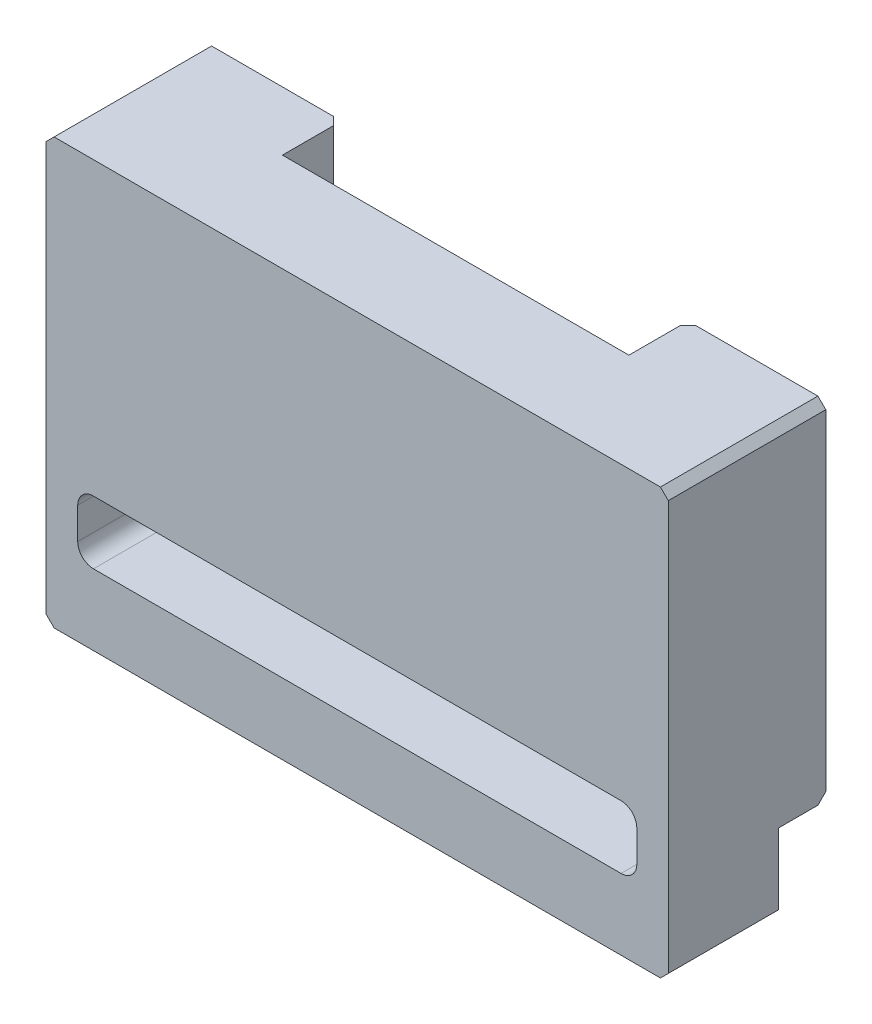
SolidWorks part; units mm, degrees
ref_plane "Front Plane" through (0, 0, 0) normal (0, 0, 1) x (1, 0, 0)
ref_plane "Top Plane" through (0, 0, 0) normal (0, 1, 0) x (1, 0, 0)
ref_plane "Right Plane" through (0, 0, 0) normal (1, 0, 0) x (0, 0, -1)
sketch "Sketch1" plane through (0, 0, 0) normal (0, 0, 1) x (1, 0, 0)
  line L0 (0, 0) -> (-42, 0) construction
  line L1 (-60.5, 5) -> (18.5, 5)
  line L2 (-60.5, 5) -> (-60.5, -49)
  line L3 (-60.5, -49) -> (18.5, -49)
  line L4 (18.5, 5) -> (18.5, -49)
  line L5 (-55.5, -39) -> (-55.5, -33) construction
  line L6 (13.5, -33) -> (13.5, -39) construction
  line L7 (6.5, -39) -> (-48.5, -39) construction
  dimension "D1" = 5
  dimension "D2" = 5
  dimension "D3" = 5
  dimension "D4" = 10
extrude "Boss-Extrude1" add sketch "Sketch1" along normal blind 5 and the other way blind 15
sketch "Sketch3" plane through (0, 0, -15) normal (0, 0, -1) x (-1, 0, 0)
  line L0 (60.5, 5) -> (60.5, -49) construction
  line L1 (-18.5, -49) -> (60.5, -49)
  line L2 (-18.5, -49) -> (-18.5, -39)
  line L3 (-18.5, -39) -> (60.5, -39)
  line L4 (60.5, -49) -> (60.5, -39)
extrude "Cut-Extrude1" cut sketch "Sketch3" against normal blind 1
sketch "Sketch4" plane through (0, 0, -15) normal (0, 0, -1) x (-1, 0, 0)
  line L1 (-14.5, -32) -> (56.5, -32)
  line L2 (56.5, -32) -> (56.5, -40)
  line L3 (-14.5, -40) -> (56.5, -40)
  line L4 (-14.5, -32) -> (-14.5, -40)
extrude "Cut-Extrude2" cut sketch "Sketch4" against normal blind 15
sketch "Sketch5" plane through (0, 0, -15) normal (0, 0, -1) x (-1, 0, 0)
  line L0 (-1, -34) -> (-1, 1)
  line L5 (-1, 1) -> (43, 1)
  line L6 (43, -34) -> (43, 1)
  line L7 (-1, -34) -> (43, -34)
extrude "Cut-Extrude3" cut sketch "Sketch5" against normal blind 2.5
sketch "Sketch6" plane through (0, 1, 0) normal (0, -1, 0) x (1, 0, 0)
  line L4 (-43, -15) -> (1, -15)
  line L5 (1, -15) -> (1, -12.5)
  line L6 (1, -12.5) -> (-43, -12.5)
  line L7 (-43, -12.5) -> (-43, -15)
  line L8 (-43, -15) -> (1, -15)
  line L9 (1, -15) -> (1, -12.5)
  line L10 (1, -12.5) -> (-43, -12.5)
  line L11 (-43, -12.5) -> (-43, -15)
  dimension "D1" = 0
extrude "Cut-Extrude4" cut sketch "Sketch6" against normal through all
sketch "Sketch7" plane through (0, 0, 0) normal (0, 0, -1) x (-1, 0, 0)
  line L4 (-14.5, -32) -> (-14.5, -40)
  line L5 (-14.5, -40) -> (56.5, -40)
  line L6 (56.5, -40) -> (56.5, -32)
  line L7 (56.5, -32) -> (-14.5, -32)
  line L8 (-14.5, -32) -> (-14.5, -40)
  line L9 (-14.5, -40) -> (56.5, -40)
  line L10 (56.5, -40) -> (56.5, -32)
  line L11 (56.5, -32) -> (-14.5, -32)
  dimension "D1" = 0
extrude "Cut-Extrude5" cut sketch "Sketch7" against normal through all
sketch "Sketch8" plane through (0, 0, -12.5) normal (0, 0, -1) x (-1, 0, 0)
  line L4 (-1, -32) -> (43, -32)
  line L5 (43, -32) -> (43, 5)
  line L6 (43, 5) -> (-1, 5)
  line L7 (-1, 5) -> (-1, -32)
  line L8 (-1, -32) -> (43, -32)
  line L9 (43, -32) -> (43, 5)
  line L10 (43, 5) -> (-1, 5)
  line L11 (-1, 5) -> (-1, -32)
  dimension "D1" = 0
extrude "Cut-Extrude6" cut sketch "Sketch8" against normal blind 5
sketch "Sketch9" plane through (0, 0, -14) normal (0, 0, -1) x (-1, 0, 0)
  line L8 (56.5, -40) -> (-14.5, -40)
  line L9 (-14.5, -40) -> (-14.5, -39)
  line L10 (-14.5, -39) -> (-18.5, -39)
  line L11 (-18.5, -39) -> (-18.5, -49)
  line L12 (-18.5, -49) -> (60.5, -49)
  line L13 (60.5, -49) -> (60.5, -39)
  line L14 (60.5, -39) -> (56.5, -39)
  line L15 (56.5, -39) -> (56.5, -40)
  line L16 (56.5, -40) -> (-14.5, -40)
  line L17 (-14.5, -40) -> (-14.5, -39)
  line L18 (-14.5, -39) -> (-18.5, -39)
  line L19 (-18.5, -39) -> (-18.5, -49)
  line L20 (-18.5, -49) -> (60.5, -49)
  line L21 (60.5, -49) -> (60.5, -39)
  line L22 (60.5, -39) -> (56.5, -39)
  line L23 (56.5, -39) -> (56.5, -40)
  dimension "D1" = 0
extrude "Cut-Extrude7" cut sketch "Sketch9" against normal blind 5
fillet "Fillet1" radius 2 4 edges at (14.5, -40, -2) (14.5, -32, -5) (-56.5, -32, -5) (-56.5, -40, -2)
chamfer "Chamfer1" distance 1 angle 45 2 edges at (14.2321, -39, -12) (-56.2321, -39, -12) first distance on face at (13.8464, -39.1107, -6.3333) first distance on face at (-55.8464, -39.1107, -6.3333)
chamfer "Chamfer2" distance 1 angle 45 2 edges at (1, -13.5, -15) (-43, -13.5, -15)
chamfer "Chamfer3" distance 1 angle 45 4 edges at (18.5, 5, -5) (18.5, -49, -2) (-60.5, 5, -5) (-60.5, -49, -2)
chamfer "Chamfer4" distance 1 angle 45 2 edges at (-58.626, -39, -15) (16.626, -39, -15)
